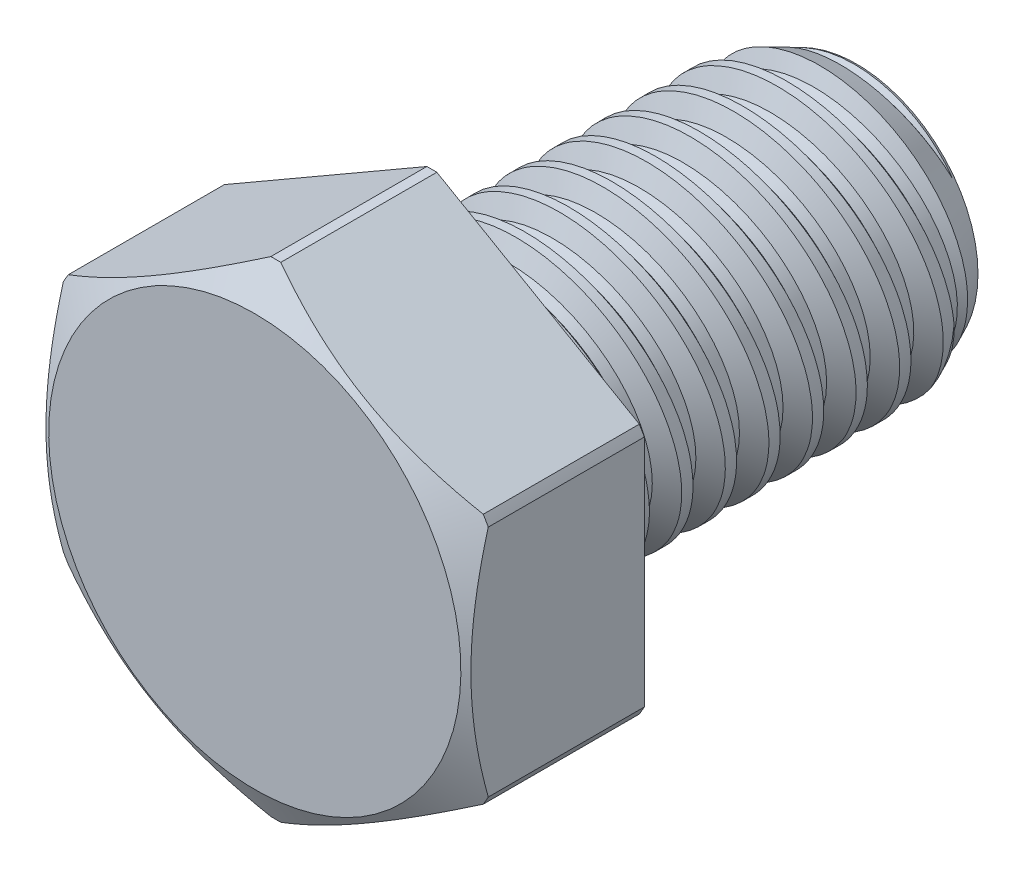
SolidWorks part; units mm, degrees
ref_plane "Front" through (0, 0, 0) normal (0, 0, 1) x (1, 0, 0)
ref_plane "Top" through (0, 0, 0) normal (0, 1, 0) x (1, 0, 0)
ref_plane "Right" through (0, 0, 0) normal (1, 0, 0) x (0, 0, -1)
sketch "Sketch1" plane through (0, 0, 0) normal (1, 0, 0) x (0, 0, -1)
  line L0 (-9.525, 0) -> (-17.4625, 0) construction
  line L1 (-9.525, 0) -> (-9.525, 9.525) construction
  line L2 (-9.525, 0) -> (-17.4625, 0) construction
  line L3 (-9.525, -6.35) -> (9.525, -6.35) construction
  line L4 (-9.525, 0) -> (9.525, 0)
  line L5 (-9.525, 0) -> (-9.525, 6.35)
  line L6 (-9.525, 6.35) -> (9.525, 6.35)
  line L7 (9.525, 0) -> (9.525, 6.35)
  dimension "Screw Dia" = 12.7
  dimension "Screw Length" = 19.05
  dimension "Head Height" = 7.9375
  dimension "Head Width" = 19.05
revolve "Revolve1" add sketch "Sketch1" angle 360 about L0
sketch "Sketch2" plane through (0, 0, 0) normal (1, 0, 0) x (0, 0, -1)
  line L0 (-9.525, 6.35) -> (-9.525, -6.35) construction
  line L1 (-9.525, -6.35) -> (-7.5712, -6.35) construction
  line L2 (-7.5712, -6.35) -> (-9.525, 6.35) construction
  line L3 (-9.525, 6.35) -> (-9.2836, 6.3871) construction
  line L4 (-7.5939, 6.6471) -> (-9.2836, 6.3871)
  line L5 (-9.2836, 6.3871) -> (-8.5193, 5.4347)
  line L6 (-8.5193, 5.4347) -> (-8.0365, 5.509)
  line L7 (-8.0365, 5.509) -> (-7.5939, 6.6471)
  line L8 (-8.2779, 5.4719) -> (-8.4387, 6.5171) construction
  line L9 (-9.525, 0) -> (-9.525, 6.35) construction
  line L10 (-9.525, 6.35) -> (-8.413, 6.35) construction
  line L11 (-8.413, 6.35) -> (-6.4592, -6.35) construction
  line L12 (-6.4592, -6.35) -> (-7.5712, -6.35) construction
  line L13 (-9.525, -6.35) -> (9.525, -6.35) construction
  line L14 (-9.525, -0.3214) -> (-5.3472, 0.3214) construction
  line L15 (-9.525, 6.35) -> (9.525, 6.35) construction
  point P17 (-7.4361, 0)
  dimension "D1" = 1.9538
  dimension "Thread Pitch" = 1.9538
  dimension "D3" = 0.4885
  dimension "D4" = 0.2442
  dimension "D5" = 60
revolve "Cut-Revolve1" cut sketch "Sketch2" angle 360 about L14
sketch "Sketch3" plane through (0, 0, 0) normal (1, 0, 0) x (0, 0, -1)
  line L0 (7.5622, 6.35) -> (9.525, 5.4347)
  line L1 (9.525, 5.4347) -> (9.525, 6.35)
  line L2 (9.525, 6.35) -> (7.5622, 6.35)
  line L3 (-9.525, 6.35) -> (9.525, 6.35) construction
  line L4 (9.525, 0) -> (9.525, 6.35) construction
  line L5 (-8.5193, 5.4347) -> (9.525, 5.4347) construction
  line L6 (7.5622, 6.35) -> (7.5622, -6.35) construction
  line L7 (-9.525, -6.35) -> (9.525, -6.35) construction
  line L8 (0, 0) -> (7.5622, 0) construction
  dimension "D1" = 25
  dimension "D2" = 12.7
revolve "Cut-Revolve2" cut sketch "Sketch3" angle 360 about L8
pattern_linear "LPattern1" count 2 spacing 1.9538 along (0, 0, 1) count 10 spacing 1.9538 along (0, 0, 1)
sketch "Sketch5" plane through (0, 0, 9.525) normal (0, 0, 1) x (1, 0, 0)
  line L1 (0, 10.9985) -> (-9.525, 5.4993)
  line L2 (-9.525, 5.4993) -> (-9.525, -5.4993)
  line L3 (-9.525, -5.4993) -> (0, -10.9985)
  line L4 (0, -10.9985) -> (9.525, -5.4993)
  line L5 (9.525, -5.4993) -> (9.525, 5.4993)
  line L6 (9.525, 5.4993) -> (0, 10.9985)
  circle A0 centre (0, 0) radius 9.525 construction
  dimension "D1" = 19.05
extrude "Extrude1" add sketch "Sketch5" along normal up to vertex
sketch "Sketch6" plane through (0, 0, 0) normal (1, 0, 0) x (0, 0, -1)
  line L0 (-17.4625, 9.2392) -> (-16.5201, 10.8715)
  line L1 (-16.5201, 10.8715) -> (-9.525, 10.8715)
  line L2 (-9.525, 10.8715) -> (-9.525, 11.3795)
  line L3 (-9.525, 11.3795) -> (-17.4625, 11.3795)
  line L4 (-17.4625, 11.3795) -> (-17.4625, 9.2392)
  line L5 (-17.4625, 5.4993) -> (-17.4625, 10.9985) construction
  line L6 (-17.4625, 10.9985) -> (-9.525, 10.9985) construction
  line L7 (-9.525, 5.4993) -> (-9.525, 10.9985) construction
  line L8 (0, 0) -> (-16.5201, 0) construction
  line L9 (-9.525, 0) -> (-17.4625, 0) construction
  line L10 (-16.5201, 0) -> (-16.5201, 10.8715) construction
  line L11 (-13.4937, 11.3795) -> (-13.4937, 0) construction
  dimension "D1" = 30
  dimension "D2" = 0.127
  dimension "D3" = 0.508
  dimension "D4" = 18.4785
  dimension "D5" = 7.9375
  dimension "D6" = 19.05
revolve "Cut-Revolve3" cut sketch "Sketch6" angle 360 about L8
equation "\"D3@Sketch2\"=\"Thread Pitch@Sketch2\"/4"
equation "\"D4@Sketch2\"=\"Thread Pitch@Sketch2\"/8"
equation "\"D1@Sketch2\"=\"Thread Pitch@Sketch2\""
equation "\"D3@LPattern1\"=\"Thread Pitch@Sketch2\""
equation "\"D4@LPattern1\"=\"Thread Pitch@Sketch2\""
equation "\"D4@Sketch6\"=\"Head Width@Sketch1\"*.97"
equation "\"D2@LPattern1\"=\"Screw Length@Sketch1\"/\"Thread Pitch@Sketch2\""
